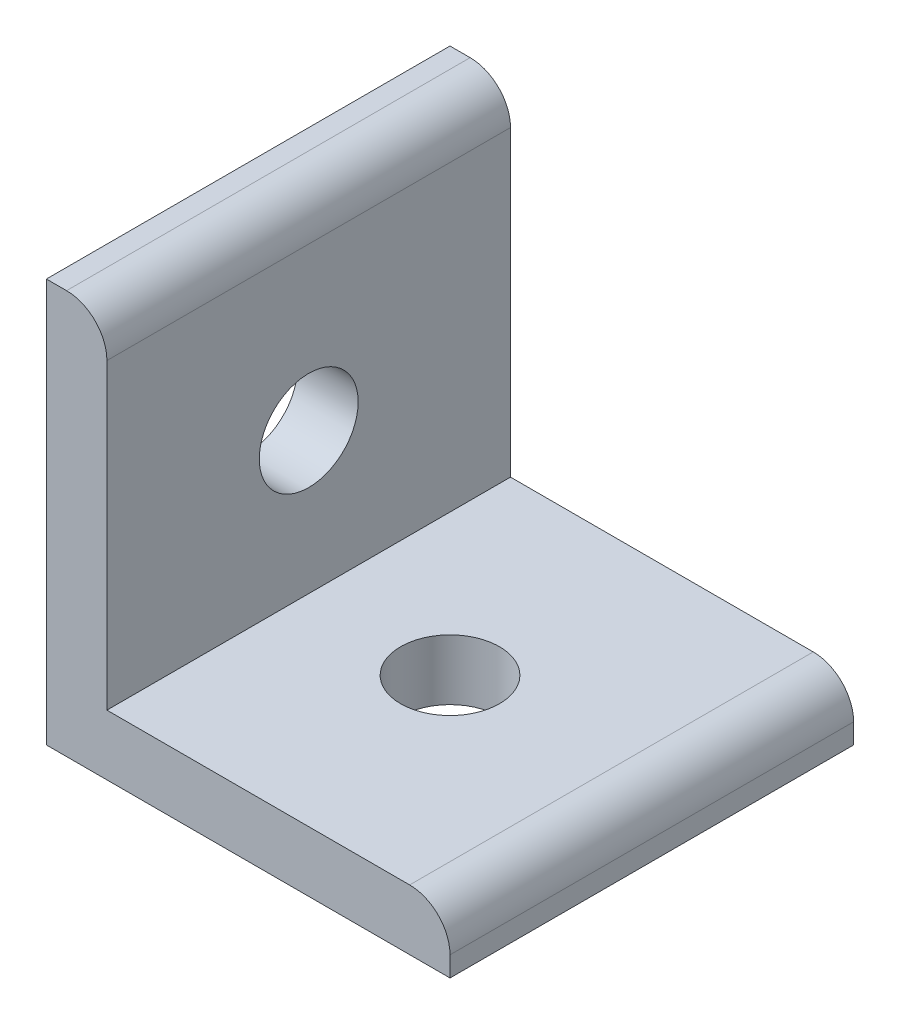
SolidWorks part; units mm, degrees
ref_plane "前视基准面" through (0, 0, 0) normal (0, 0, 1) x (1, 0, 0)
ref_plane "上视基准面" through (0, 0, 0) normal (0, 1, 0) x (1, 0, 0)
ref_plane "右视基准面" through (0, 0, 0) normal (1, 0, 0) x (0, 0, -1)
sketch "草图1" plane through (0, 0, 0) normal (0, 0, 1) x (1, 0, 0)
  line L0 (0, 0) -> (20.0016, 0)
  line L1 (0, 0) -> (0, 19.9969)
  line L2 (0, 19.9969) -> (2.9992, 19.9969)
  line L3 (2.9992, 19.9969) -> (2.9992, 2.9944)
  line L4 (2.9992, 2.9944) -> (20.0016, 2.9944)
  line L5 (20.0016, 2.9944) -> (20.0016, 0)
  dimension "D1" = 17.0024
  dimension "D2" = 17.0024
  dimension "D3" = 2.9992
  dimension "D4" = 2.9944
extrude "凸台-拉伸1" add sketch "草图1" along normal blind 20
sketch "草图3" plane through (2.9992, 0, 0) normal (1, 0, 0) x (0, 0, -1)
  line L0 (-20, 19.9969) -> (0, 19.9969) construction
  circle A0 centre (-10, 9.9969) radius 2.45
  dimension "D1" = 4.9
  dimension "D2" = 10
extrude "切除-拉伸1" cut sketch "草图3" against normal up to surface (2.9992 mm away) up to face at (0, 9.9984, 10)
sketch "草图5" plane through (0, 2.9944, 0) normal (0, 1, 0) x (1, 0, 0)
  line L0 (20.0016, -20) -> (20.0016, 0) construction
  circle A0 centre (10.0016, -10) radius 2.45
  dimension "D1" = 4.9
  dimension "D2" = 10
extrude "切除-拉伸2" cut sketch "草图5" against normal up to surface (2.9944 mm away) up to face at (10.0008, 0, 10)
fillet "圆角1" radius 2 1 edges at (2.9992, 19.9969, 10)
fillet "圆角2" radius 2 1 edges at (20.0016, 2.9944, 10)
